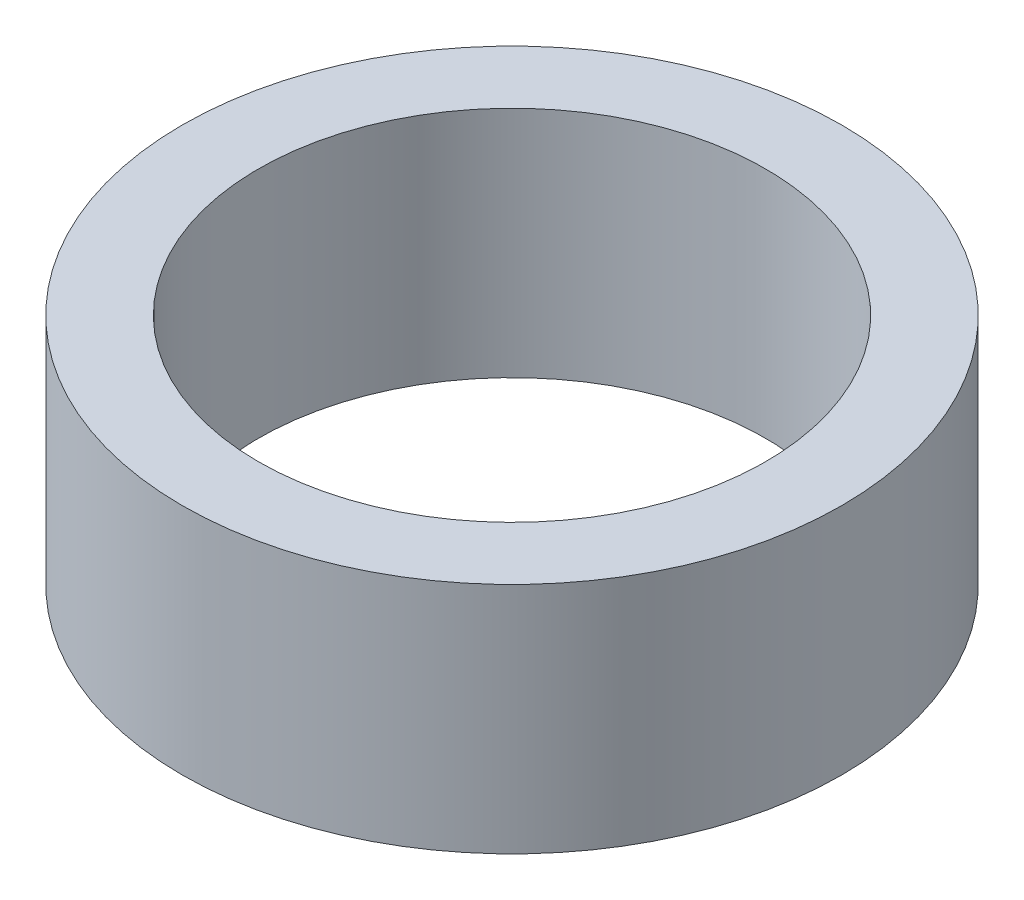
SolidWorks part; units mm, degrees
ref_plane "Front Plane" through (0, 0, 0) normal (0, 0, 1) x (1, 0, 0)
ref_plane "Top Plane" through (0, 0, 0) normal (0, 1, 0) x (1, 0, 0)
ref_plane "Right Plane" through (0, 0, 0) normal (1, 0, 0) x (0, 0, -1)
sketch "Sketch1" plane through (0, 0, 0) normal (0, 1, 0) x (1, 0, 0)
  circle A0 centre (0, 0) radius 32.5
  dimension "FLANGE_OD" = 65
extrude "Boss-Extrude1" add sketch "Sketch1" along normal blind 23
sketch "Sketch2" plane through (0, 0, 0) normal (0, 1, 0) x (1, 0, 0)
  circle A0 centre (0, 0) radius 25
  dimension "BORE_D" = 50
extrude "Cut-Extrude1" cut sketch "Sketch2" along normal through all
sketch "Sketch3" plane through (0, 23, 0) normal (0, 1, 0) x (1, 0, 0)
  circle A0 centre (0, 0) radius 14.0589 construction
  circle A1 centre (-14.0589, 0) radius 1.5
  dimension "BOLT_D" = 3
  dimension "BOLT_PCD" = 28.1179
extrude "Cut-Extrude2" cut sketch "Sketch3" against normal blind 17.0343 rebuild error yes
pattern_circular "CirPattern1" count 8 over 360 rebuild error yes
